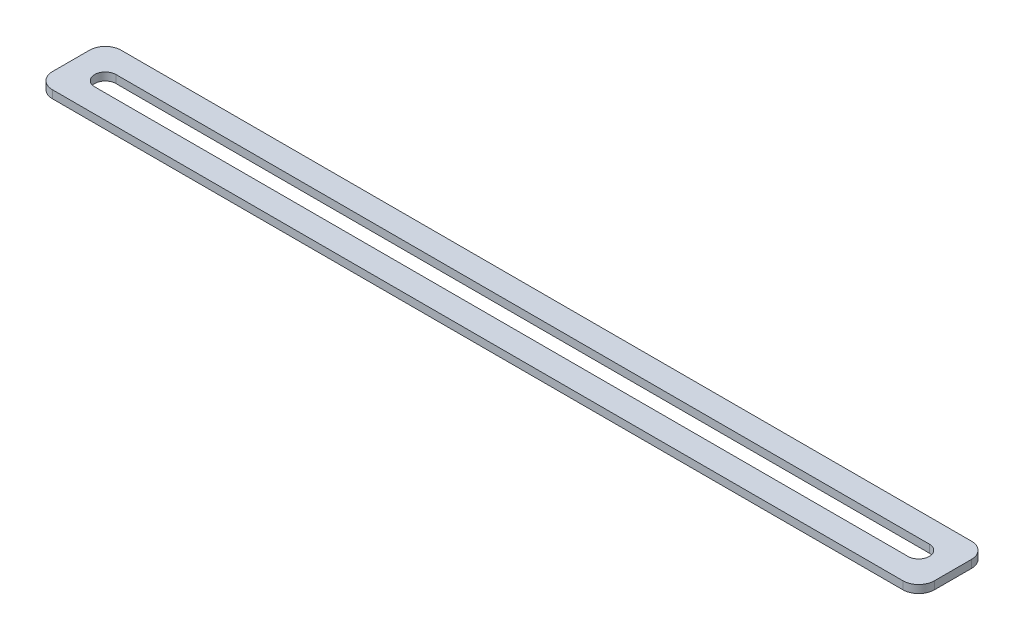
SolidWorks part; units mm, degrees
material "AISI 4130 Steel, annealed at 865C"
ref_plane "Front Plane" through (0, 0, 0) normal (0, 0, 1) x (1, 0, 0)
ref_plane "Top Plane" through (0, 0, 0) normal (0, 1, 0) x (1, 0, 0)
ref_plane "Right Plane" through (0, 0, 0) normal (1, 0, 0) x (0, 0, -1)
sketch "Sketch1" plane through (0, 0, 0) normal (0, 1, 0) x (1, 0, 0)
  line L0 (-81.9875, 0) -> (81.9875, 0) construction
  line L1 (-88.9, -6.9125) -> (88.9, -6.9125)
  line L2 (-88.9, -6.9125) -> (-88.9, 6.9125)
  line L3 (-88.9, 6.9125) -> (88.9, 6.9125)
  line L4 (88.9, -6.9125) -> (88.9, 6.9125)
  line L5 (-88.9, -6.9125) -> (88.9, 6.9125) construction
  line L6 (-88.9, 6.9125) -> (88.9, -6.9125) construction
  line L7 (-81.9875, 2.15) -> (81.9875, 2.15)
  line L8 (-81.9875, -2.15) -> (81.9875, -2.15)
  arc A0 (-81.9875, 2.15) -> (-81.9875, -2.15) centre (-81.9875, 0) ccw
  arc A1 (81.9875, -2.15) -> (81.9875, 2.15) centre (81.9875, 0) ccw
  point P0 (0, 0)
  point P8 (0, 0)
  dimension "D2" = 4.7625
  dimension "D3" = 2.15
  dimension "D1" = 177.8
  dimension "D4" = 4.7625
extrude "Boss-Extrude1" add sketch "Sketch1" along normal blind 1.5875
fillet "Fillet1" radius 3.175 4 edges at (88.9, 0.7937, -6.9125) (88.9, 0.7937, 6.9125) (-88.9, 0.7937, -6.9125) (-88.9, 0.7937, 6.9125)
